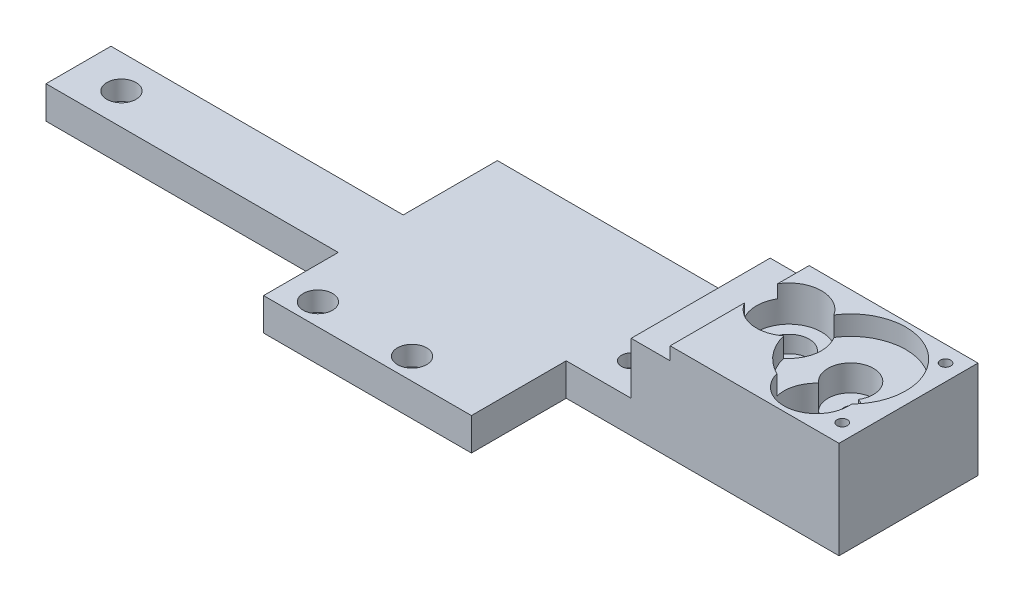
SolidWorks part; units mm, degrees
ref_plane "前视基准面" through (0, 0, 0) normal (0, 0, 1) x (1, 0, 0)
ref_plane "上视基准面" through (0, 0, 0) normal (0, 1, 0) x (1, 0, 0)
ref_plane "右视基准面" through (0, 0, 0) normal (1, 0, 0) x (0, 0, -1)
other "Configuration Table"
sketch "草图1" plane through (0, 0, 0) normal (0, 1, 0) x (1, 0, 0)
  line L33 (0, -21.4) -> (42, -21.4)
  line L34 (0, -21.4) -> (0, 0)
  line L35 (0, 0) -> (42, 0)
  line L36 (42, -21.4) -> (42, 0)
  point P0 (-90.6464, 22.0667)
  dimension "D3" = 21.4
  dimension "D6" = 42
extrude "凸台-拉伸1" add sketch "草图1" along normal blind 12 contours L33 L36 L35 L34 | L33 | L34 region at (21, 0, 10.7)
sketch "草图2" plane through (0, 0, 0) normal (0, 0, -1) x (-1, 0, 0)
  line L0 (0, 12) -> (-42, 12) construction
  line L1 (0, 0) -> (-10, 0)
  line L2 (0, 0) -> (0, 10)
  line L3 (0, 10) -> (-10, 10)
  line L4 (-10, 0) -> (-10, 10)
  line L6 (-10, 0) -> (-16, 0)
  line L7 (-10, 0) -> (-10, 2)
  line L8 (-10, 2) -> (-16, 2)
  line L9 (-16, 0) -> (-16, 2)
  dimension "D1" = 2
  dimension "D2" = 10
  dimension "D3" = 2
  dimension "D4" = 6
extrude "切除-拉伸1" cut sketch "草图2" against normal through all contours L7 L8 L9 L6 | L4 L3 L2 L1
sketch "草图3" plane through (0, 0, 0) normal (0, -1, 0) x (1, 0, 0)
  circle A0 centre (20.3, 7.4) radius 5
  circle A1 centre (31.6497, 9.2532) radius 1.05
  circle A4 centre (31.6497, 9.2532) radius 8.5
  circle A6 centre (32.7692, 15.656) radius 5
  circle A7 centre (31.6497, 9.2532) radius 3.5
  circle A8 centre (20.3, 7.4) radius 3.1
  circle A10 centre (32.7692, 15.656) radius 3.1
  circle A11 centre (32.7692, 15.656) radius 2
  dimension "D1" = 10
  dimension "D2" = 17
  dimension "D3" = 7
  dimension "D4" = 10
  dimension "D5" = 6.2
  dimension "D6" = 4
  dimension "D7" = 6.2
  dimension "D8" = 2.1
extrude "切除-拉伸2" cut sketch "草图3" against normal blind 5.5 contours A0
extrude "切除-拉伸3" cut sketch "草图3<3>" against normal blind 3 contours A4
sketch "草图3<3>" plane through (0, 0, 0) normal (0, -1, 0) x (1, 0, 0) same geometry as "草图3"
extrude "切除-拉伸4" cut sketch "草图3<4>" against normal blind 7 contours A7
sketch "草图3<4>" plane through (0, 0, 0) normal (0, -1, 0) x (1, 0, 0) same geometry as "草图3"
extrude "切除-拉伸5" cut sketch "草图3<5>" against normal blind 8.5 contours A6
sketch "草图3<5>" plane through (0, 0, 0) normal (0, -1, 0) x (1, 0, 0) same geometry as "草图3"
extrude "切除-拉伸6" cut sketch "草图3<6>" against normal blind 2.6 from surface contours A10 starting at face at (32.7692, 8.5, 10.656)
sketch "草图3<6>" plane through (0, 0, 0) normal (0, -1, 0) x (1, 0, 0) same geometry as "草图3"
extrude "切除-拉伸7" cut sketch "草图3<7>" against normal blind 2.6 from surface contours A8 starting at face at (20.3, 5.5, 2.4)
sketch "草图3<7>" plane through (0, 0, 0) normal (0, -1, 0) x (1, 0, 0) same geometry as "草图3"
sketch "草图4" plane through (0, 12, 0) normal (0, 1, 0) x (1, 0, 0)
  line L1 (42, 0) -> (-32, 0)
  line L2 (42, 0) -> (42, -36)
  line L3 (42, -36) -> (-32, -36)
  line L4 (-32, 0) -> (-32, -36)
  line L5 (0, -21.4) -> (0, 0) construction
  line L10 (-32, -14.5) -> (-77, -14.5)
  line L11 (-32, -14.5) -> (-32, -24.5)
  line L12 (-32, -24.5) -> (-77, -24.5)
  line L13 (-77, -14.5) -> (-77, -24.5)
  line L14 (42, -21.4) -> (0, -21.4)
  line L15 (42, -21.4) -> (42, -36)
  line L16 (42, -36) -> (0, -36)
  line L17 (0, -21.4) -> (0, -36)
  line M5 (0, -21.4) -> (42, -21.4)
  line M6 (42, -21.4) -> (42, 0)
  line M7 (42, 0) -> (0, 0)
  line M8 (0, 0) -> (0, -21.4)
  dimension "D1" = 36
  dimension "D2" = 74
  dimension "D3" = 45
  dimension "D4" = 10
  dimension "D5" = 14.5
extrude "凸台-拉伸2" add sketch "草图4" along normal blind 5 from surface contours M8 M5 M6 M7 | L17 L1 L4 L3 M8 | L10 L13 L12 L4 region at (21, 12, 10.7) region at (-16, 12, 18) region at (-54.5, 12, 19.5) starting at face at (5, 10, 10.7)
sketch "草图5" plane through (0, 10, 0) normal (0, -1, 0) x (1, 0, 0)
  circle A0 centre (-70.2308, 19.656) radius 1.5
  circle A1 centre (-21.9808, 32.656) radius 1.5
  circle A2 centre (-7.4808, 32.656) radius 1.5
  circle A3 centre (-7.4808, 32.656) radius 2.25
  circle A4 centre (-21.9808, 32.656) radius 2.25
  circle A5 centre (-70.2308, 19.656) radius 2.25
  dimension "D1" = 3
  dimension "D2" = 4.5
extrude "切除-拉伸8" cut sketch "草图5" against normal offset from surface (3 mm away) 2 contours A5 | A4 | A3 up to face at (-19.8, 15, 19.28)
extrude "切除-拉伸9" cut sketch "草图5<3>" against normal through all contours A0 | A1 | A2
sketch "草图5<3>" plane through (0, 10, 0) normal (0, -1, 0) x (1, 0, 0) same geometry as "草图5"
extrude "切除-拉伸10" cut sketch "草图3<8>" against normal through all contours A11 | A1
sketch "草图3<8>" plane through (0, 0, 0) normal (0, -1, 0) x (1, 0, 0) same geometry as "草图3"
sketch "草图6" plane through (0, 15, 0) normal (0, 1, 0) x (1, 0, 0)
  circle A0 centre (5, -5) radius 2.25
  circle A1 centre (5, -16.4) radius 2.25
  circle A2 centre (5, -5) radius 1.5
  circle A3 centre (5, -16.4) radius 1.5
  dimension "D1" = 3
  dimension "D2" = 4.5
extrude "切除-拉伸11" cut sketch "草图6" against normal through all contours A2 | A3
extrude "切除-拉伸12" cut sketch "草图6<3>" against normal offset from surface (3 mm away) 2 contours A1 | A0 up to face at (3.5, 10, 5)
sketch "草图6<3>" plane through (0, 15, 0) normal (0, 1, 0) x (1, 0, 0) same geometry as "草图6"
sketch "草图7" plane through (0, 0, 0) normal (0, -1, 0) x (1, 0, 0)
  line L0 (16, 21.4) -> (42, 21.4) construction
  line L1 (42, 21.4) -> (42, 0) construction
  line L2 (16, 0) -> (42, 0) construction
  circle A0 centre (39.5, 18.4) radius 0.8
  circle A1 centre (39.5, 2.5) radius 0.8
  dimension "D1" = 1.6
  dimension "D2" = 3
  dimension "D3" = 2.5
  dimension "D4" = 2.5
  dimension "D5" = 2.5
extrude "切除-拉伸13" cut sketch "草图7" against normal blind 4 contours A1 | A0
extrude "切除-拉伸14" cut sketch "草图3<9>" against normal blind 2.6 from surface contours A10 starting at face at (32.7692, 8.5, 12.556)
sketch "草图3<9>" plane through (0, 0, 0) normal (0, -1, 0) x (1, 0, 0) same geometry as "草图3"
ref_plane "基准面1" through (0, -10, 0) normal (0, 1, 0) x (1, 0, 0)
mirror "镜向2" about plane through (0, -10, 0) normal (0, 1, 0) of bodies 200
sketch "草图8" plane through (0, -10, 0) normal (0, 1, 0) x (1, 0, 0)
  line L1 (-103.2655, 19.9217) -> (72.4791, 19.9217)
  line L2 (-103.2655, 19.9217) -> (-103.2655, -56.0576)
  line L3 (-103.2655, -56.0576) -> (72.4791, -56.0576)
  line L4 (72.4791, 19.9217) -> (72.4791, -56.0576)
extrude "切除-拉伸15" cut sketch "草图8" along normal through all
sketch "草图9" plane through (0, -30, 0) normal (0, 1, 0) x (1, 0, 0)
  line L1 (-32, -24.5) -> (0, -24.5)
  line L2 (-32, -24.5) -> (-32, -36)
  line L3 (-32, -36) -> (0, -36)
  line L4 (0, -24.5) -> (0, -36)
extrude "凸台-拉伸3" add sketch "草图9" against normal through all
sketch "草图10" plane through (0, -30, 0) normal (0, 1, 0) x (1, 0, 0)
  circle A0 centre (-26.9808, -32.656) radius 2.25
  circle A1 centre (-26.9808, -32.656) radius 1.5
  circle A2 centre (-12.4808, -32.656) radius 2.25
  circle A3 centre (-12.4808, -32.656) radius 1.5
  point P6 (-12.4808, -32.656)
  point P8 (-29.9808, -31.046)
  point P9 (-26.9808, -32.656)
  point P11 (0, 0)
  point P12 (0, 0)
  dimension "D1" = 3
  dimension "D2" = 4.5
extrude "切除-拉伸16" cut sketch "草图10" against normal through all contours A3 | A1
extrude "切除-拉伸17" cut sketch "草图10<4>" against normal offset from surface (3 mm away) 2 contours A0 | A2
sketch "草图10<4>" plane through (0, -30, 0) normal (0, 1, 0) x (1, 0, 0) same geometry as "草图10"
